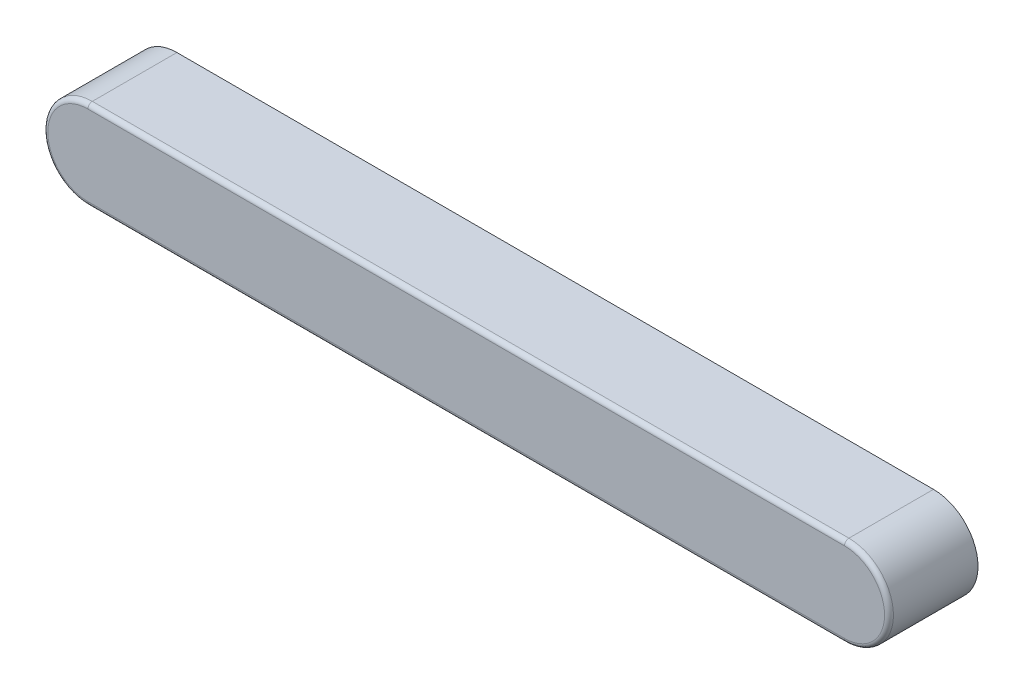
SolidWorks part; units mm, degrees
ref_plane "前视基准面" through (0, 0, 0) normal (0, 0, 1) x (1, 0, 0)
ref_plane "上视基准面" through (0, 0, 0) normal (0, 1, 0) x (1, 0, 0)
ref_plane "右视基准面" through (0, 0, 0) normal (1, 0, 0) x (0, 0, -1)
other "Configuration Table"
sketch "草图1" plane through (0, 0, 0) normal (0, 0, 1) x (1, 0, 0)
  line L1 (-8.4848, 5.1061) -> (8.5152, 5.1061)
  line L3 (-8.4848, 3.1061) -> (8.5152, 3.1061)
  arc A0 (-8.4848, 5.1061) -> (-8.4848, 3.1061) centre (-8.4848, 4.1061) ccw
  arc A1 (8.5152, 3.1061) -> (8.5152, 5.1061) centre (8.5152, 4.1061) ccw
  dimension "D1" = 17
  dimension "D2" = 2
extrude "凸台-拉伸1" add sketch "草图1" along normal blind 2
fillet "圆角1" radius 0.1 4 edges at (0.0152, 5.1061, 2) (9.5152, 4.1061, 2) (0.0152, 3.1061, 2) (-9.4848, 4.1061, 2)
